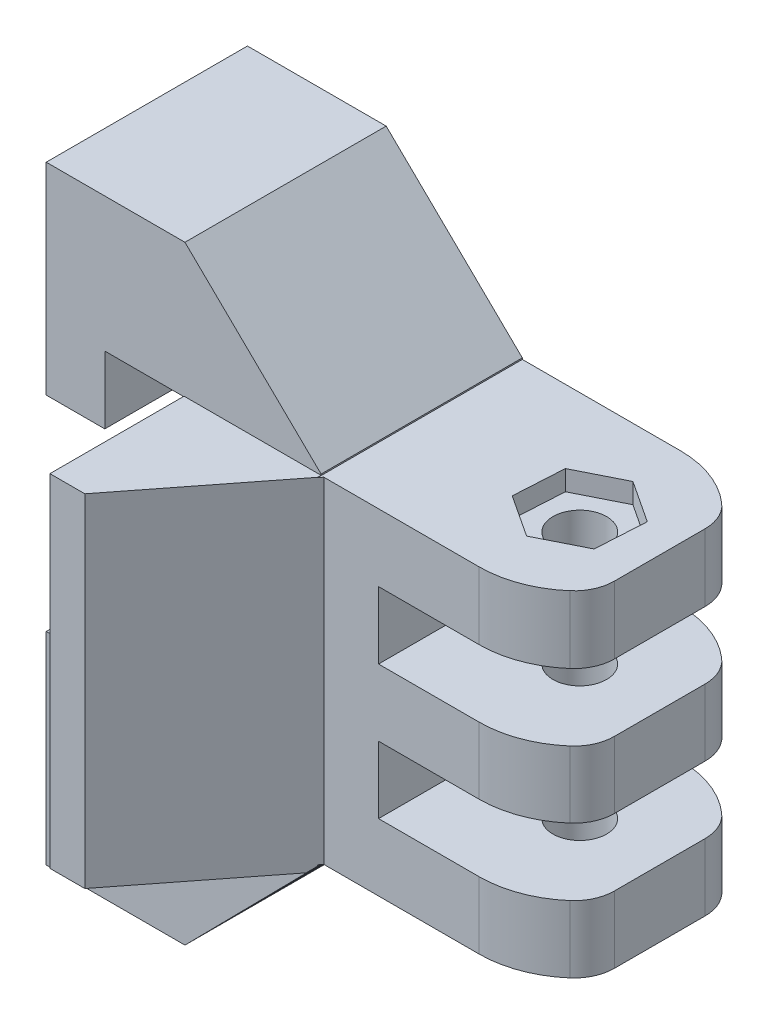
SolidWorks part; units mm, degrees
ref_plane "Front Plane" through (0, 0, 0) normal (0, 0, 1) x (1, 0, 0)
ref_plane "Top Plane" through (0, 0, 0) normal (0, 1, 0) x (1, 0, 0)
ref_plane "Right Plane" through (0, 0, 0) normal (1, 0, 0) x (0, 0, -1)
sketch "Sketch1" plane through (0, 0, 0) normal (0, 0, 1) x (1, 0, 0)
  line L0 (27.2728, 35.3866) -> (20.4907, 35.3866)
  line L1 (20.4907, 35.3866) -> (20.4907, 35.4872)
  line L2 (20.4907, 35.4872) -> (10.3408, 45.376)
  line L3 (10.3408, 45.376) -> (0, 45.376)
  line L4 (0, 45.376) -> (0, 30.3389)
  line L5 (0, 30.3389) -> (4.3656, 30.3389)
  line L6 (4.3656, 30.3389) -> (4.3656, 35.366)
  line L7 (4.3656, 35.366) -> (10.2747, 35.366)
  line L8 (10.2747, 35.366) -> (10.2747, 25.0913)
  line L9 (10.2747, 25.0913) -> (1.2788, 25.0913)
  line L10 (1.2788, 25.0913) -> (1.2788, 20.3729)
  line L11 (1.2788, 20.3729) -> (10.2747, 20.3729)
  line L12 (10.2747, 20.3729) -> (10.2747, 9.9219)
  line L13 (10.2747, 9.9219) -> (4.3656, 9.9219)
  line L14 (4.3656, 9.9219) -> (4.3656, 15.0812)
  line L15 (4.3656, 15.0812) -> (0, 15.0812)
  line L16 (0, 15.0812) -> (0, 0)
  line L17 (0, 0) -> (10.3408, 0)
  line L18 (10.3408, 0) -> (20.4907, 10.3043)
  line L19 (20.4907, 10.3043) -> (20.4907, 10.387)
  line L20 (20.4907, 10.387) -> (27.2728, 10.387)
  line L21 (27.2728, 10.387) -> (39.7726, 10.387)
  line L22 (39.7726, 10.387) -> (39.7726, 15.3834)
  line L23 (39.7726, 15.3834) -> (24.7726, 15.3834)
  line L24 (24.7726, 15.3834) -> (24.7726, 20.3833)
  line L25 (24.7726, 20.3833) -> (39.7726, 20.3833)
  line L26 (39.7726, 20.3833) -> (39.7726, 22.8868)
  line L27 (39.7726, 22.8868) -> (39.7726, 25.3628)
  line L28 (39.7726, 25.3628) -> (24.7726, 25.3628)
  line L29 (24.7726, 25.3628) -> (24.7726, 30.3627)
  line L30 (24.7726, 30.3627) -> (39.7726, 30.3627)
  line L31 (39.7726, 30.3627) -> (39.7726, 35.3866)
  line L32 (39.7726, 35.3866) -> (27.2728, 35.3866)
extrude "Boss-Extrude1" add sketch "Sketch1" along normal blind 15
fillet "Fillet1" radius 7.5 6 edges at (39.7726, 32.8747, 0) (39.7726, 22.873, 0) (39.7726, 12.8852, 0) (39.7726, 32.8747, 15) (39.7726, 22.873, 15) (39.7726, 12.8852, 15)
sketch "Sketch2" plane through (0, 10.387, 0) normal (0, -1, 0) x (1, 0, 0)
  circle A0 centre (32.2726, 7.5) radius 2
extrude "Cut-Extrude1" cut sketch "Sketch2" against normal through all
sketch "Sketch3" plane through (0, 10.387, 0) normal (0, -1, 0) x (-1, 0, 0)
  circle A0 centre (-32.2726, -7.5) radius 4.5
extrude "Cut-Extrude2" cut sketch "Sketch3" against normal blind 0.6
sketch "Sketch4" plane through (0, 35.3866, 0) normal (0, 1, 0) x (1, 0, 0)
  line L1 (35.6243, -5.8182) -> (32.492, -3.7564)
  line L2 (32.492, -3.7564) -> (29.1403, -5.4382)
  line L3 (29.1403, -5.4382) -> (28.9209, -9.1818)
  line L4 (28.9209, -9.1818) -> (32.0532, -11.2436)
  line L5 (32.0532, -11.2436) -> (35.4049, -9.5618)
  line L6 (35.4049, -9.5618) -> (35.6243, -5.8182)
  circle A0 centre (32.2726, -7.5) radius 3.75 construction
extrude "Cut-Extrude3" cut sketch "Sketch4" against normal blind 1.5
sketch "Sketch5" plane through (0, 35.3866, 0) normal (0, 1, 0) x (1, 0, 0)
  line L1 (38.2336, 3.7728) -> (49.5745, 3.7728)
  line L2 (38.2336, 3.7728) -> (38.2336, -21.0628)
  line L3 (38.2336, -21.0628) -> (49.5745, -21.0628)
  line L4 (49.5745, 3.7728) -> (49.5745, -21.0628)
extrude "Cut-Extrude4" cut sketch "Sketch5" against normal through all
fillet "Fillet2" radius 3 6 edges at (38.2336, 22.873, 2.9484) (38.2336, 32.8747, 2.9484) (38.2336, 32.8747, 12.0516) (38.2336, 22.873, 12.0516) (38.2336, 12.8852, 12.0516) (38.2336, 12.8852, 2.9484)
sketch "Sketch6" plane through (0, 0, 15) normal (0, 0, 1) x (1, 0, 0)
  line L1 (10.2747, 9.9219) -> (12.6899, 9.9219)
  line L2 (10.2747, 9.9219) -> (10.2747, 35.4061)
  line L3 (10.2747, 35.4061) -> (12.6899, 35.4061)
  line L4 (12.6899, 9.9219) -> (12.6899, 35.4061)
extrude "Boss-Extrude2" add sketch "Sketch6" along normal blind 10
chamfer "Chamfer1" distance 8 angle 52 1 edges at (12.6899, 22.664, 15) first distance on face at (16.1737, 23.2147, 15)
